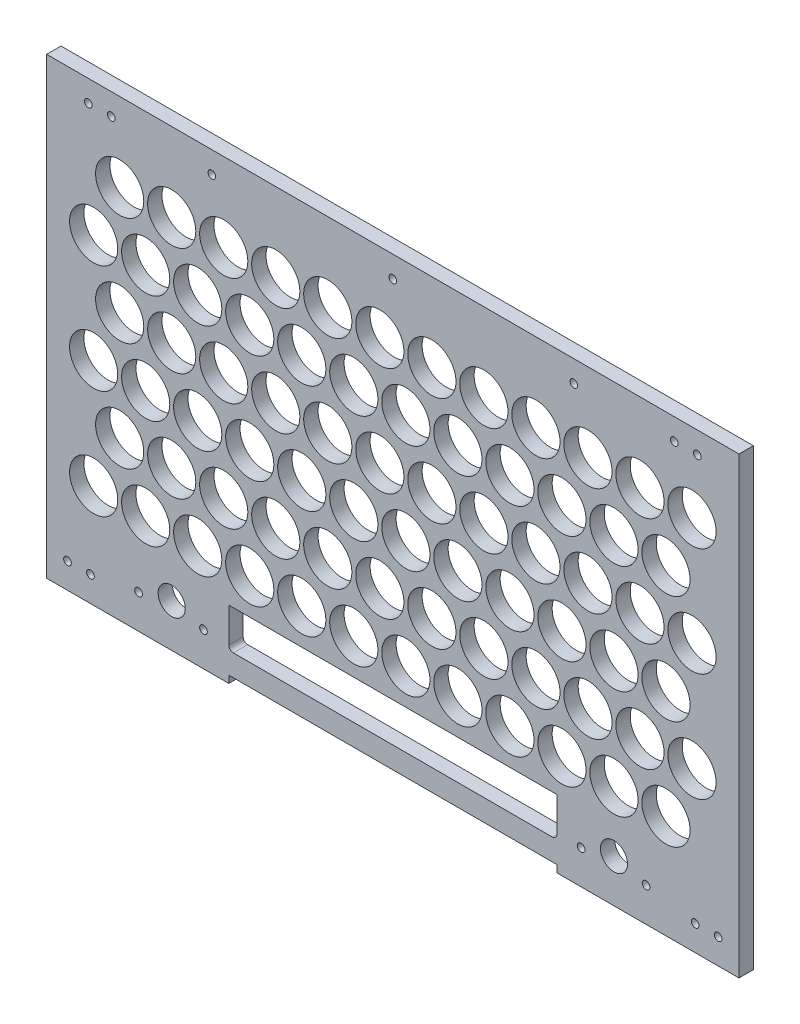
SolidWorks part; units mm, degrees
material "ABS"
ref_plane "X-Y Datum" through (0, 0, 0) normal (0, 0, 1) x (1, 0, 0)
ref_plane "X-Z Datum" through (0, 0, 0) normal (0, 1, 0) x (1, 0, 0)
ref_plane "Y-Z Datum" through (0, 0, 0) normal (1, 0, 0) x (0, 0, -1)
sketch "Sketch1" plane through (0, 0, 0) normal (0, 0, 1) x (1, 0, 0)
  line L1 (-143.025, 70.775) -> (143.025, 70.775)
  line L2 (-143.025, 70.775) -> (-143.025, -70.775)
  line L3 (-143.025, -70.775) -> (143.025, -70.775)
  line L4 (143.025, 70.775) -> (143.025, -70.775)
  line L5 (-143.025, 70.775) -> (143.025, -70.775) construction
  line L6 (-143.025, -70.775) -> (143.025, 70.775) construction
  line L13 (-153.025, -105.775) -> (153.025, -105.775)
  line L14 (-153.025, 91.65) -> (153.025, 91.65)
  line L15 (-153.025, 91.65) -> (-153.025, -105.775)
  line L16 (153.025, 91.65) -> (153.025, -105.775)
  line L17 (153.025, 70.775) -> (153.025, -70.775) construction
  line L18 (-143.025, 91.65) -> (143.025, 91.65) construction
  line L19 (-143.025, -105.775) -> (143.025, -105.775) construction
  line L20 (-153.025, 70.775) -> (-153.025, -70.775) construction
  line L21 (-132.25, -60) -> (-109.25, -60) construction
  circle A0 centre (-132.25, -60) radius 10.775
  circle A1 centre (-109.25, -60) radius 10.775 construction
  circle A2 centre (-120.75, -36) radius 10.775
  point P0 (0, 0)
  point P16 (-120.75, -60)
  dimension "D1" = 21.55
  dimension "D2" = 23
  dimension "D3" = 24
  dimension "D5" = 141.55
  dimension "D6" = 286.05
  dimension "D7" = 35
  dimension "D8" = 20.875
  dimension "D9" = 10
  dimension "D10" = 10
extrude "Boss-Extrude1" add sketch "Sketch1" along normal blind 6.35 contours A0 L3 L4 L1 L2 A2 | A2 | A0 | A0 L2 L3 | L1 L4 L3 L2 region at (2.4105, 0.9241, 0) region at (-140.6182, -68.3682, 0) region at (-132.25, -60, 0) region at (-149.383, -7.0625, 0) region at (-120.75, -36, 0)
sketch "Sketch3" plane through (0, 0, 6.35) normal (0, 0, 1) x (1, 0, 0)
  line L4 (143.025, 70.775) -> (-143.025, 70.775)
  line L5 (143.025, -70.775) -> (143.025, 70.775)
  line L6 (-143.025, -70.775) -> (143.025, -70.775)
  line L7 (-143.025, 70.775) -> (-143.025, -70.775)
  line L8 (143.025, 70.775) -> (-143.025, 70.775)
  line L9 (143.025, -70.775) -> (143.025, 70.775)
  line L10 (-143.025, -70.775) -> (143.025, -70.775)
  line L11 (-143.025, 70.775) -> (-143.025, -70.775)
  circle A0 centre (-132.25, -60) radius 10.6512
  circle A1 centre (-120.75, -36) radius 10.775
  circle A2 centre (-120.75, -36) radius 10.775 construction
  circle A3 centre (-132.25, -60) radius 10.775
  circle A4 centre (-132.25, -60) radius 10.775 construction
  circle A5 centre (-120.75, -36) radius 10.6512
  dimension "D4" = 21.3024
  dimension "D1" = 0
  dimension "D2" = 0
  dimension "D3" = 0
extrude "Cut-Extrude1" cut sketch "Sketch3" against normal through all contours A4 | A0 region at (-132.25, -60, 6.35)
sketch "Sketch4" plane through (0, 0, 6.35) normal (0, 0, 1) x (1, 0, 0)
  line L4 (143.025, 70.775) -> (-143.025, 70.775)
  line L5 (143.025, -70.775) -> (143.025, 70.775)
  line L6 (-143.025, -70.775) -> (143.025, -70.775)
  line L7 (-143.025, 70.775) -> (-143.025, -70.775)
  line L8 (143.025, 70.775) -> (-143.025, 70.775)
  line L9 (143.025, -70.775) -> (143.025, 70.775)
  line L10 (-143.025, -70.775) -> (143.025, -70.775)
  line L11 (-143.025, 70.775) -> (-143.025, -70.775)
  line L12 (143.025, 70.775) -> (-143.025, 70.775)
  line L13 (-143.025, 70.775) -> (-143.025, -70.775)
  line L14 (-143.025, -70.775) -> (143.025, -70.775)
  line L15 (143.025, -70.775) -> (143.025, 70.775)
  line L16 (143.025, 70.775) -> (-143.025, 70.775)
  line L17 (-143.025, 70.775) -> (-143.025, -70.775)
  line L18 (-143.025, -70.775) -> (143.025, -70.775)
  line L19 (143.025, -70.775) -> (143.025, 70.775)
  circle A1 centre (-120.75, -36) radius 10.6512
  circle A3 centre (-120.75, -36) radius 10.6512
  circle A5 centre (-132.25, -60) radius 10.6512
  circle A6 centre (-132.25, -60) radius 10.6512
  dimension "D4" = 0
  dimension "D1" = 0
  dimension "D2" = 0
  dimension "D3" = 0
extrude "Cut-Extrude2" cut sketch "Sketch4" against normal through all contours A3 region at (-120.75, -36, 6.35)
pattern_linear "LPattern1" count 12 spacing 23 along (1, 0, 0) of "Cut-Extrude1", "Cut-Extrude2"
pattern_linear "LPattern2" count 3 spacing 48 along (0, 1, 0) of "LPattern1"
sketch "Sketch5" plane through (0, 0, 0) normal (0, 0, -1) x (-1, 0, 0)
sketch "Sketch13" plane through (0, 91.65, 0) normal (0, 1, 0) x (1, 0, 0)
  line L4 (153.025, 0) -> (-153.025, 0)
  line L5 (-153.025, 0) -> (-153.025, -6.35)
  line L6 (-153.025, -6.35) -> (153.025, -6.35)
  line L7 (153.025, -6.35) -> (153.025, 0)
  line L8 (153.025, 0) -> (-153.025, 0)
  line L9 (-153.025, 0) -> (-153.025, -6.35)
  line L10 (-153.025, -6.35) -> (153.025, -6.35)
  line L11 (153.025, -6.35) -> (153.025, 0)
  dimension "D1" = 0
extrude "Boss-Extrude2" add sketch "Sketch13" along normal blind 3.175
sketch "Sketch14" plane through (0, 0, 0) normal (0, 0, -1) x (-1, 0, 0)
  circle A0 centre (-97.75, -86.775) radius 6
extrude "Cut-Extrude3" cut sketch "Sketch14" against normal through all
mirror "Mirror1" about plane through (0, 0, 0) normal (1, 0, 0) of "Cut-Extrude3"
sketch "Sketch15" plane through (0, 0, 0) normal (0, 0, -1) x (-1, 0, 0)
  point P0 (-111.94, -90.775)
  point P1 (-83.25, -90.775)
  point P3 (83.712, -90.775)
  point P11 (80, 85.3)
  point P13 (0, 85.3)
  point P15 (-80, 85.3)
  point P41 (112.402, -90.775)
  point P47 (-143.8175, -94.6)
  point P50 (-133.6575, -94.6)
  point P54 (-134.61, 85.3)
  point P57 (-124.45, 85.3)
  point P61 (124.45, 85.3)
  point P64 (134.61, 85.3)
  point P68 (133.6575, -94.6)
  point P71 (143.8175, -94.6)
hole_wizard "M3 Clearance Hole1" positions "Sketch15" profile "Sketch16" hole size "M3" standard "ANSI Metric" end condition through all
sketch "Sketch16" plane through (111.94, -90.775, 0) normal (1, 0, 0) x (0, 1, 0)
  line L0 (0, 0) -> (0, 6.35)
  line L1 (0, 6.35) -> (1.7, 6.35)
  line L2 (1.7, 6.35) -> (1.7, 0)
  line L5 (1.7, 0) -> (0, 0)
  line L11 (0, -6.35) -> (0, 107.95) construction
  dimension "Thru Hole Dia." = 3.4
  dimension "Thru Hole Depth" = 6.35
sketch "Sketch17" plane through (0, 0, 0) normal (0, 0, -1) x (-1, 0, 0)
  line L0 (0, -105.775) -> (0, -77.9164) construction
  line L1 (153.025, -105.775) -> (-153.025, -105.775) construction
  circle A0 centre (0, -90.775) radius 2.25
  circle A1 centre (140.6256, 12) radius 2.25
  circle A2 centre (-140.6875, -12) radius 2.25
  point P0 (-140.6875, -12)
  point P1 (140.6256, 12)
  point P9 (0, -90.775)
  point P11 (83.712, -90.775)
  dimension "D1" = 4.5
extrude "Cut-Extrude4" [suppressed] cut sketch "Sketch17" against normal through all
sketch "Sketch18" plane through (0, -105.775, 0) normal (0, -1, 0) x (1, 0, 0)
  line L0 (0, 0) -> (0, 6.35)
  line L1 (-153.025, 0) -> (153.025, 0) construction
  line L2 (-153.025, 6.35) -> (153.025, 6.35) construction
  line L4 (-72.5, 6.35) -> (72.5, 6.35)
  line L5 (-72.5, 6.35) -> (-72.5, 0)
  line L6 (-72.5, 0) -> (72.5, 0)
  line L7 (72.5, 6.35) -> (72.5, 0)
  line L8 (-72.5, 6.35) -> (72.5, 0) construction
  line L9 (-72.5, 0) -> (72.5, 6.35) construction
  point P6 (0, 3.175)
  line M3 (-153.025, 0) -> (153.025, 0)
  line M5 (153.025, 6.35) -> (-153.025, 6.35)
  dimension "D1" = 145
extrude "Cut-Extrude5" cut sketch "Sketch18" against normal blind 30 contours L7 L0 M5 M3 | L5 L0 M5 M3 region at (-36.25, -105.775, 3.175) region at (36.25, -105.775, 3.175)
fillet "Fillet1" [suppressed] radius 8
sketch "Sketch19" plane through (0, 0, 0) normal (0, 0, -1) x (-1, 0, 0)
  line L0 (-72.5, -75.775) -> (-72.5, -105.775) construction
  line L1 (-72.5, -102.6) -> (72.5, -102.6)
  line L2 (-72.5, -102.6) -> (-72.5, -93.075)
  line L3 (-72.5, -93.075) -> (72.5, -93.075)
  line L4 (72.5, -102.6) -> (72.5, -93.075)
  line L5 (72.5, -75.775) -> (72.5, -105.775) construction
  line L6 (-72.5, -105.775) -> (-153.025, -105.775) construction
  dimension "D1" = 3.175
  dimension "D2" = 9.525
extrude "Boss-Extrude3" add sketch "Sketch19" against normal blind 6.35
fillet "Fillet2" radius 2 2 edges at (72.5, -93.075, 3.175) (-72.5, -93.075, 3.175)
